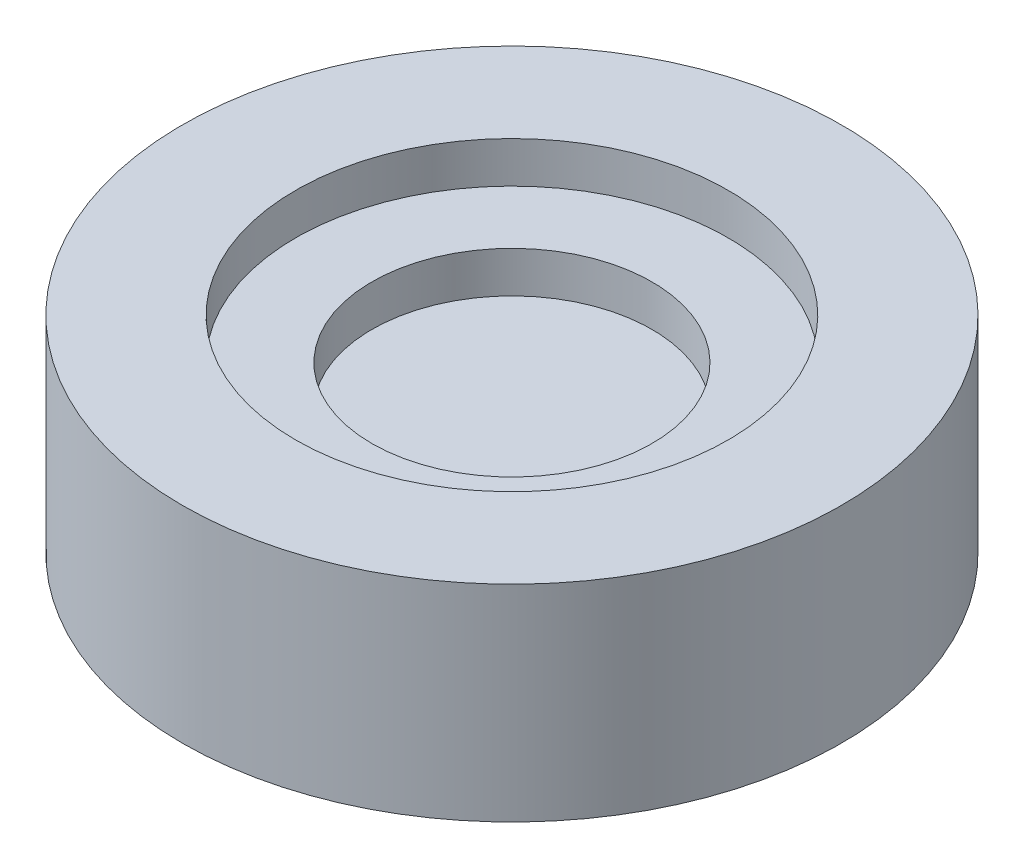
SolidWorks part; units mm, degrees
ref_plane "Спереди" through (0, 0, 0) normal (0, 0, 1) x (1, 0, 0)
ref_plane "Сверху" through (0, 0, 0) normal (0, 1, 0) x (1, 0, 0)
ref_plane "Справа" through (0, 0, 0) normal (1, 0, 0) x (0, 0, -1)
ref_axis "Axis1" through (0, 0, 0) along (0, 1, 0)
sketch "Sketch1" plane through (0, 0, 0) normal (0, 1, 0) x (1, 0, 0)
  circle A0 centre (0, 0) radius 8
  dimension "D1" = 16
extrude "Boss-Extrude1" add sketch "Sketch1" along normal blind 5
sketch "Sketch2" plane through (0, 0, 0) normal (0, -1, 0) x (1, 0, 0)
  line L1 (-3.2, -1.6) -> (3.2, -1.6)
  line L2 (-3.2, -1.6) -> (-3.2, 1.6)
  line L3 (-3.2, 1.6) -> (3.2, 1.6)
  line L4 (3.2, -1.6) -> (3.2, 1.6)
  line L5 (-3.2, -1.6) -> (3.2, 1.6) construction
  line L6 (-3.2, 1.6) -> (3.2, -1.6) construction
  point P0 (0, 0)
  dimension "D1" = 3.2
  dimension "D2" = 6.4
extrude "Cut-Extrude1" cut sketch "Sketch2" against normal blind 2
sketch "Sketch3" plane through (0, 0, 0) normal (0, 0, 1) x (1, 0, 0)
  line L0 (0, 0) -> (0, -50000) construction
  line L1 (-8, 0) -> (8, 0) construction
  line L2 (0, 3) -> (-3.4, 3)
  line L3 (-3.4, 3) -> (-3.4, 4)
  line L4 (-3.4, 4) -> (-5.25, 4)
  line L5 (-5.25, 4) -> (-5.25, 5)
  line L6 (8, 5) -> (-8, 5) construction
  line L7 (-5.25, 5) -> (0, 5)
  line L8 (0, 5) -> (0, 3)
  point P4 (0, 0)
  dimension "D1" = 6.8
  dimension "D2" = 10.5
  dimension "D3" = 1
  dimension "D4" = 1
revolve "Cut-Revolve1" cut sketch "Sketch3" angle 360 about L0
equation "\"D2@Sketch2\"=\"D1@Sketch2\"*2"
